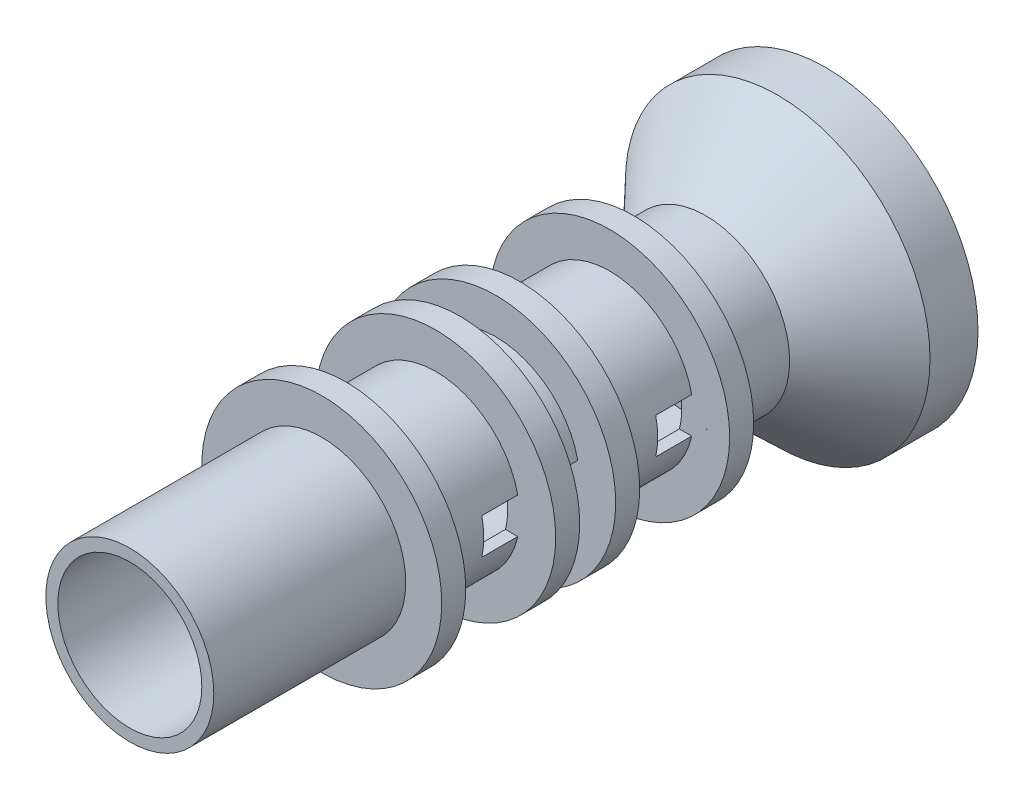
SolidWorks part; units mm, degrees
material "ABS"
ref_plane "正面" through (0, 0, 0) normal (0, 0, 1) x (1, 0, 0)
ref_plane "平面" through (0, 0, 0) normal (0, 1, 0) x (1, 0, 0)
ref_plane "右側面" through (0, 0, 0) normal (1, 0, 0) x (0, 0, -1)
sketch "ｽｹｯﾁ1" plane through (0, 0, 0) normal (0, 0, 1) x (1, 0, 0)
  circle A0 centre (0, 0) radius 3.5 construction
  circle A1 centre (0, 0) radius 6.35
  dimension "D1" = 7
  dimension "D2" = 12.7
ref_plane "平面1" through (0, 0, 5) normal (0, 0, 1) x (1, 0, 0)
sketch "ｽｹｯﾁ2" plane through (0, 0, 5) normal (0, 0, 1) x (1, 0, 0)
  circle A0 centre (0, 0) radius 3.5 construction
  circle A1 centre (0, 0) radius 3.5
ref_plane "平面2" through (0, 0, 29) normal (0, 0, 1) x (1, 0, 0)
ref_plane "平面3" through (0, 0, 24) normal (0, 0, 1) x (1, 0, 0)
sketch "ｽｹｯﾁ5" plane through (0, 0, 29) normal (0, 0, 1) x (1, 0, 0)
  circle A0 centre (0, 0) radius 6.35 construction
  circle A1 centre (0, 0) radius 6.35 construction
  circle A2 centre (0, 0) radius 3.5
  dimension "D1" = 7
extrude "ﾎﾞｽ - 押し出し3" add sketch "ｽｹｯﾁ2" along normal up to surface (19 mm away) contours A1 up to plane "平面3"
extrude "ﾎﾞｽ - 押し出し4" add sketch "ｽｹｯﾁ1" along normal blind 2 separate body
extrude "ﾎﾞｽ - 押し出し5" add sketch "ｽｹｯﾁ5" against normal blind 2
loft "ﾛﾌﾄ1" add section face at (6.35, 0, 2) section face at (3.5, 0, 5) connector at (-0.1759, 6.3476, 2) connector at (-0.0742, 3.4992, 5)
loft "ﾛﾌﾄ2" add section face at (3.5, 0, 24) section face at (3.5, 0, 27) connector at (-0.0749, 3.4992, 24) connector at (-0.0751, 3.4992, 27)
ref_plane "平面5" through (0, 0, 14.5) normal (0, 0, 1) x (1, 0, 0)
ref_plane "平面6" through (0, 0, 15.25) normal (0, 0, 1) x (1, 0, 0)
sketch "ｽｹｯﾁ9" plane through (0, 0, 15.25) normal (0, 0, 1) x (1, 0, 0)
  circle A0 centre (0, 0) radius 5
  dimension "D1" = 10
extrude "ﾎﾞｽ - 押し出し6" add sketch "ｽｹｯﾁ9" along normal blind 1
ref_plane "平面7" through (0, 0, 20) normal (0, 0, 1) x (1, 0, 0)
sketch "ｽｹｯﾁ10" plane through (0, 0, 20) normal (0, 0, 1) x (1, 0, 0)
  circle A1 centre (0, 0) radius 5
  circle A2 centre (0, 0) radius 5
  dimension "D1" = 0
extrude "ﾎﾞｽ - 押し出し7" add sketch "ｽｹｯﾁ10" along normal blind 1
mirror "ﾐﾗｰ3" about plane through (0, 0, 14.5) normal (0, 0, 1) of "ﾎﾞｽ - 押し出し7", "ﾎﾞｽ - 押し出し6"
sketch "ｽｹｯﾁ6" plane through (0, 0, 0) normal (0, 0, -1) x (-1, 0, 0)
  circle A0 centre (0, 0) radius 2.75
  dimension "D1" = 5.5
extrude "ｶｯﾄ - 押し出し1" cut sketch "ｽｹｯﾁ6" against normal blind 3
sketch "ｽｹｯﾁ7" plane through (0, 0, 3) normal (0, 0, -1) x (-1, 0, 0)
  circle A0 centre (0, 0) radius 1.8
  dimension "D1" = 3.6
extrude "ｶｯﾄ - 押し出し2" cut sketch "ｽｹｯﾁ7" against normal through all
sketch "ｽｹｯﾁ8" plane through (0, 0, 29) normal (0, 0, 1) x (1, 0, 0)
  circle A0 centre (0, 0) radius 3
  dimension "D1" = 6
extrude "ｶｯﾄ - 押し出し3" cut sketch "ｽｹｯﾁ8" against normal offset from surface (23 mm away) 3 up to face at (-1.8, 0, 3)
ref_plane "平面9" through (3.5, 0, 0) normal (1, 0, 0) x (0, 0, -1)
sketch "ｽｹｯﾁ11" plane through (3.5, 0, 0) normal (1, 0, 0) x (0, 0, -1)
  line L0 (0, 0) -> (-29, 0) construction
  line L1 (-29, 6.9851) -> (-29, -6.9851) construction
  line L2 (-16.25, 3.5) -> (-16.25, -3.5) construction
  line L3 (-17.75, 0.75) -> (-16.25, 0.75)
  line L4 (-17.75, 0.75) -> (-17.75, -0.75)
  line L5 (-17.75, -0.75) -> (-16.25, -0.75)
  line L6 (-16.25, 0.75) -> (-16.25, -0.75)
  line L7 (-17.75, 0.75) -> (-16.25, -0.75) construction
  line L8 (-17.75, -0.75) -> (-16.25, 0.75) construction
  line L9 (-13.75, 5) -> (-13.75, -5) construction
  line L10 (-15.25, 0.75) -> (-13.75, 0.75)
  line L11 (-15.25, 0.75) -> (-15.25, -0.75)
  line L12 (-15.25, -0.75) -> (-13.75, -0.75)
  line L13 (-13.75, 0.75) -> (-13.75, -0.75)
  line L14 (-15.25, 0.75) -> (-13.75, -0.75) construction
  line L15 (-15.25, -0.75) -> (-13.75, 0.75) construction
  line L16 (-9, 3.5) -> (-9, -3.5) construction
  line L17 (-10.5, 0.75) -> (-9, 0.75)
  line L18 (-10.5, 0.75) -> (-10.5, -0.75)
  line L19 (-10.5, -0.75) -> (-9, -0.75)
  line L20 (-9, 0.75) -> (-9, -0.75)
  line L21 (-10.5, 0.75) -> (-9, -0.75) construction
  line L22 (-10.5, -0.75) -> (-9, 0.75) construction
  point P5 (-17, 0)
  point P12 (-14.5, 0)
  point P19 (-9.75, 0)
  dimension "D1" = 1.5
  dimension "D2" = 1.5
extrude "ｶｯﾄ - 押し出し4" cut sketch "ｽｹｯﾁ11" against normal up to next
sketch "ｽｹｯﾁ12" plane through (0, 0, 0) normal (0, 0, -1) x (-1, 0, 0)
  line L0 (0, 0) -> (0, 2.75) construction
  line L1 (0, 0) -> (0.3745, 2.7244) construction
  line L2 (0, 0) -> (0.7419, 2.648) construction
  line L3 (0, 0) -> (1.0956, 2.5223) construction
  line L4 (0, 0) -> (1.4289, 2.3497) construction
  line L5 (0, 0) -> (1.7355, 2.1332) construction
  line L6 (0, 0) -> (2.0098, 1.877) construction
  line L7 (0, 0) -> (2.2467, 1.5859) construction
  line L8 (0, 0) -> (2.4417, 1.2652) construction
  line L9 (0, 0) -> (2.5912, 0.9209) construction
  line L10 (0, 0) -> (2.6925, 0.5595) construction
  line L11 (0, 0) -> (2.7436, 0.1877) construction
  line L12 (0, 0) -> (2.7436, -0.1877) construction
  line L13 (0, 0) -> (2.6925, -0.5595) construction
  line L14 (0, 0) -> (2.5912, -0.9209) construction
  line L15 (0, 0) -> (2.4417, -1.2652) construction
  line L16 (0, 0) -> (2.2467, -1.5859) construction
  line L17 (0, 0) -> (2.0098, -1.877) construction
  line L18 (0, 0) -> (1.7355, -2.1332) construction
  line L19 (0, 0) -> (1.4289, -2.3497) construction
  line L20 (0, 0) -> (1.0956, -2.5223) construction
  line L21 (0, 0) -> (0.7419, -2.648) construction
  line L22 (0, 0) -> (0.3745, -2.7244) construction
  line L23 (0, 0) -> (0, -2.75) construction
  line L24 (0, 0) -> (-0.3745, -2.7244) construction
  line L25 (0, 0) -> (-0.7419, -2.648) construction
  line L26 (0, 0) -> (-1.0956, -2.5223) construction
  line L27 (0, 0) -> (-1.4289, -2.3497) construction
  line L28 (0, 0) -> (-1.7355, -2.1332) construction
  line L29 (0, 0) -> (-2.0098, -1.877) construction
  line L30 (0, 0) -> (-2.2467, -1.5859) construction
  line L31 (0, 0) -> (-2.4417, -1.2652) construction
  line L32 (0, 0) -> (-2.5912, -0.9209) construction
  line L33 (0, 0) -> (-2.6925, -0.5595) construction
  line L34 (0, 0) -> (-2.7436, -0.1877) construction
  line L35 (0, 0) -> (-2.7436, 0.1877) construction
  line L36 (0, 0) -> (-2.6925, 0.5595) construction
  line L37 (0, 0) -> (-2.5912, 0.9209) construction
  line L38 (0, 0) -> (-2.4417, 1.2652) construction
  line L39 (0, 0) -> (-2.2467, 1.5859) construction
  line L40 (0, 0) -> (-2.0098, 1.877) construction
  line L41 (0, 0) -> (-1.7355, 2.1332) construction
  line L42 (0, 0) -> (-1.4289, 2.3497) construction
  line L43 (0, 0) -> (-1.0956, 2.5223) construction
  line L44 (0, 0) -> (-0.7419, 2.648) construction
  line L45 (0, 0) -> (-0.3745, 2.7244) construction
  line L46 (0, 0) -> (0.2081, 3.0429) construction
  line L47 (0.2081, 3.0429) -> (-0.0626, 2.7493)
  line L48 (-0.0626, 2.7493) -> (0, 0) construction
  line L49 (0, 0) -> (0.4364, 2.7152) construction
  line L50 (0.4364, 2.7152) -> (0.2081, 3.0429)
  line L51 (1.0214, 2.8739) -> (0.6815, 2.6642)
  line L52 (1.1527, 2.4967) -> (1.0214, 2.8739)
  line L53 (1.7589, 2.4918) -> (1.375, 2.3816)
  line L54 (1.7836, 2.0931) -> (1.7589, 2.4918)
  line L55 (2.3659, 1.9248) -> (1.9666, 1.9223)
  line L56 (2.2822, 1.5343) -> (2.3659, 1.9248)
  line L57 (2.7975, 1.2151) -> (2.4123, 1.3204)
  line L58 (2.6115, 0.8617) -> (2.7975, 1.2151)
  line L59 (3.0216, 0.4153) -> (2.679, 0.6206)
  line L60 (2.7472, 0.1252) -> (3.0216, 0.4153)
  line L61 (3.0216, -0.4153) -> (2.7472, -0.1252)
  line L62 (2.679, -0.6206) -> (3.0216, -0.4153)
  line L63 (2.7975, -1.2151) -> (2.6115, -0.8617)
  line L64 (2.4123, -1.3204) -> (2.7975, -1.2151)
  line L65 (2.3659, -1.9248) -> (2.2822, -1.5343)
  line L66 (1.9666, -1.9223) -> (2.3659, -1.9248)
  line L67 (1.7589, -2.4918) -> (1.7836, -2.0931)
  line L68 (1.375, -2.3816) -> (1.7589, -2.4918)
  line L69 (1.0214, -2.8739) -> (1.1527, -2.4967)
  line L70 (0.6815, -2.6642) -> (1.0214, -2.8739)
  line L71 (0.2081, -3.0429) -> (0.4364, -2.7152)
  line L72 (-0.0626, -2.7493) -> (0.2081, -3.0429)
  line L73 (-0.6205, -2.9862) -> (-0.3123, -2.7322)
  line L74 (-0.802, -2.6304) -> (-0.6205, -2.9862)
  line L75 (-1.4032, -2.708) -> (-1.0379, -2.5466)
  line L76 (-1.482, -2.3165) -> (-1.4032, -2.708)
  line L77 (-2.0818, -2.229) -> (-1.6865, -2.1722)
  line L78 (-2.052, -1.8308) -> (-2.0818, -2.229)
  line L79 (-2.606, -1.5847) -> (-2.21, -1.6366)
  line L80 (-2.4699, -1.2093) -> (-2.606, -1.5847)
  line L81 (-2.9369, -0.8229) -> (-2.5696, -0.9797)
  line L82 (-2.7045, -0.4981) -> (-2.9369, -0.8229)
  line L83 (-3.05, 0) -> (-2.7386, -0.2501)
  line L84 (-2.7386, 0.2501) -> (-3.05, 0)
  line L85 (-2.9369, 0.8229) -> (-2.7045, 0.4981)
  line L86 (-2.5696, 0.9797) -> (-2.9369, 0.8229)
  line L87 (-2.606, 1.5847) -> (-2.4699, 1.2093)
  line L88 (-2.21, 1.6366) -> (-2.606, 1.5847)
  line L89 (-2.0818, 2.229) -> (-2.052, 1.8308)
  line L90 (-1.6865, 2.1722) -> (-2.0818, 2.229)
  line L91 (-1.4032, 2.708) -> (-1.482, 2.3165)
  line L92 (-1.0379, 2.5466) -> (-1.4032, 2.708)
  line L93 (-0.6205, 2.9862) -> (-0.802, 2.6304)
  line L94 (-0.3123, 2.7322) -> (-0.6205, 2.9862)
  circle A0 centre (0, 0) radius 2.75 construction
  circle A1 centre (0, 0) radius 3.05 construction
  arc A2 (0, 2.75) -> (0.3745, 2.7244) centre (0, 0) cw construction
  circle A3 centre (0, 0) radius 2.75 construction
  arc A4 (-0.0626, 2.7493) -> (0.4364, 2.7152) centre (0, 0) cw
  arc A5 (0.6815, 2.6642) -> (1.1527, 2.4967) centre (0, 0) cw
  arc A6 (1.375, 2.3816) -> (1.7836, 2.0931) centre (0, 0) cw
  arc A7 (1.9666, 1.9223) -> (2.2822, 1.5343) centre (0, 0) cw
  arc A8 (2.4123, 1.3204) -> (2.6115, 0.8617) centre (0, 0) cw
  arc A9 (2.679, 0.6206) -> (2.7472, 0.1252) centre (0, 0) cw
  arc A10 (2.7472, -0.1252) -> (2.679, -0.6206) centre (0, 0) cw
  arc A11 (2.6115, -0.8617) -> (2.4123, -1.3204) centre (0, 0) cw
  arc A12 (2.2822, -1.5343) -> (1.9666, -1.9223) centre (0, 0) cw
  arc A13 (1.7836, -2.0931) -> (1.375, -2.3816) centre (0, 0) cw
  arc A14 (1.1527, -2.4967) -> (0.6815, -2.6642) centre (0, 0) cw
  arc A15 (0.4364, -2.7152) -> (-0.0626, -2.7493) centre (0, 0) cw
  arc A16 (-0.3123, -2.7322) -> (-0.802, -2.6304) centre (0, 0) cw
  arc A17 (-1.0379, -2.5466) -> (-1.482, -2.3165) centre (0, 0) cw
  arc A18 (-1.6865, -2.1722) -> (-2.052, -1.8308) centre (0, 0) cw
  arc A19 (-2.21, -1.6366) -> (-2.4699, -1.2093) centre (0, 0) cw
  arc A20 (-2.5696, -0.9797) -> (-2.7045, -0.4981) centre (0, 0) cw
  arc A21 (-2.7386, -0.2501) -> (-2.7386, 0.2501) centre (0, 0) cw
  arc A22 (-2.7045, 0.4981) -> (-2.5696, 0.9797) centre (0, 0) cw
  arc A23 (-2.4699, 1.2093) -> (-2.21, 1.6366) centre (0, 0) cw
  arc A24 (-2.052, 1.8308) -> (-1.6865, 2.1722) centre (0, 0) cw
  arc A25 (-1.482, 2.3165) -> (-1.0379, 2.5466) centre (0, 0) cw
  arc A26 (-0.802, 2.6304) -> (-0.3123, 2.7322) centre (0, 0) cw
  point P53 (0, 0)
  point P54 (0.1877, 2.7436)
  point P56 (0.1877, 2.7436)
  point P129 (0, 0)
  dimension "D2" = 6.1
  dimension "D3" = 10.435
  dimension "D1" = 46
  dimension "D4" = 23
extrude "ｶｯﾄ - 押し出し5" cut sketch "ｽｹｯﾁ12" against normal up to surface (3 mm away) up to face at (-1.8, 0, 3)
equation "\"D3@ｽｹｯﾁ12\"=360/23*2/3"
